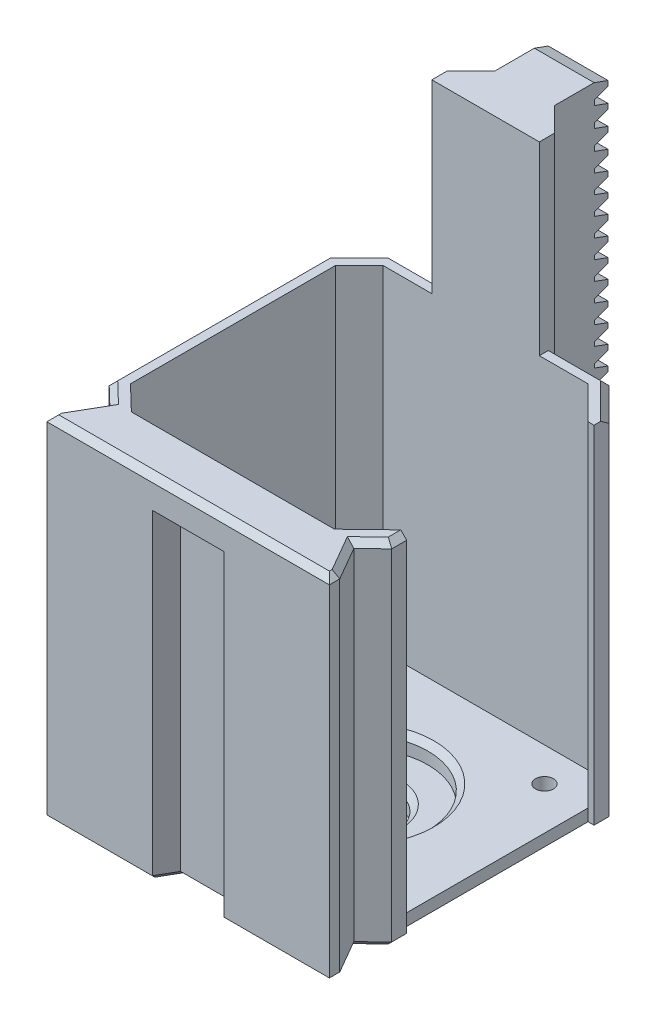
SolidWorks part; units mm, degrees
ref_plane "Front Plane" through (0, 0, 0) normal (0, 0, 1) x (1, 0, 0)
ref_plane "Top Plane" through (0, 0, 0) normal (0, 1, 0) x (1, 0, 0)
ref_plane "Right Plane" through (0, 0, 0) normal (1, 0, 0) x (0, 0, -1)
sketch "Sketch1" plane through (0, 0, 0) normal (0, 1, 0) x (1, 0, 0)
  line L0 (-21.15, 17.15) -> (-17.15, 21.15)
  line L1 (-17, -21.15) -> (17, -21.15)
  line L2 (-21.15, -17.15) -> (-21.15, 17.15)
  line L3 (-17.15, 21.15) -> (17.15, 21.15)
  line L4 (21.15, -17.15) -> (21.15, 17.15)
  line L5 (-21.15, -21.15) -> (21.15, 21.15) construction
  line L6 (-21.15, 21.15) -> (21.15, -21.15) construction
  line L7 (-21.15, -17.15) -> (-17, -21.15)
  line L8 (17, -21.15) -> (21.15, -17.15)
  line L9 (17.15, 21.15) -> (21.15, 17.15)
  circle A0 centre (-15.5, 15.5) radius 1.5
  circle A1 centre (15.5, 15.5) radius 1.5
  circle A2 centre (15.5, -15.5) radius 1.5
  circle A3 centre (-15.5, -15.5) radius 1.5
  circle A4 centre (0, 0) radius 11.5
  point P0 (0, 0)
  dimension "D3" = 3
  dimension "D4" = 3
  dimension "D9" = 3
  dimension "D10" = 3
  dimension "D12" = 23
  dimension "D1" = 42.3
  dimension "D2" = 42.3
  dimension "D11" = 31
  dimension "D13" = 34
  dimension "D6" = 4
  dimension "D7" = 4
extrude "Mount Face Extrude" add sketch "Sketch1" along normal blind 3
chamfer "Bracket Mount Hole Chamfer" distance 0.75 angle 45 4 edges at (-15.5, 0, -14) (15.5, 0, -14) (15.5, 0, 17) (-15.5, 0, 17)
sketch "Sketch5" plane through (0, 0, 0) normal (0, 1, 0) x (1, 0, 0)
  line L0 (21.15, -17.15) -> (22.65, -15.7042)
  line L1 (23.65, -14.7404) -> (23.65, 14.65) construction
  line L3 (-24.65, -28.65) -> (24.65, -28.65) construction
  line L5 (-23.65, -26.9179) -> (-23.65, -28.65)
  line L6 (-23.65, -28.65) -> (23.65, -28.65)
  line L7 (23.65, -28.65) -> (23.65, -26.9179)
  line L8 (-23.65, -26.9179) -> (-24.65, -28.65) construction
  line L9 (24.65, -28.65) -> (23.65, -26.9179) construction
  line L10 (22.65, 15.65) -> (23.65, 15.65)
  line L11 (22.65, -15.7042) -> (23.65, -15.7042)
  line L12 (23.65, 14.65) -> (23.65, 15.65) construction
  line L13 (22.65, 15.65) -> (23.65, 14.65) construction
  line L14 (23.65, -15.7042) -> (23.65, -14.7404) construction
  line L15 (22.65, -15.7042) -> (23.65, -14.7404) construction
  line L16 (-23.65, 18.1855) -> (-23.65, -18.2126)
  line L17 (-23.65, -18.2126) -> (-18.0087, -23.65)
  line L18 (-18.0087, -23.65) -> (18.0087, -23.65)
  line L19 (18.0087, -23.65) -> (23.65, -18.2126)
  line L20 (23.65, -18.2126) -> (23.65, 18.1855)
  line L21 (23.65, 18.1855) -> (18.1855, 23.65)
  line L22 (18.1855, 23.65) -> (-18.1855, 23.65)
  line L23 (-18.1855, 23.65) -> (-23.65, 18.1855)
  line L24 (-23.65, 14.65) -> (-23.65, -18.2126)
  line L25 (-23.65, -18.2126) -> (-20.4209, -21.325)
  line L26 (-18.0087, -23.65) -> (18.0087, -23.65) construction
  line L27 (20.4209, -21.325) -> (23.65, -18.2126)
  line L28 (23.65, -18.2126) -> (23.65, -15.7042)
  line L29 (23.65, 18.1855) -> (18.1855, 23.65)
  line L30 (18.1855, 23.65) -> (-18.1855, 23.65)
  line L31 (-18.1855, 23.65) -> (-23.65, 18.1855)
  line L32 (-21.15, 17.15) -> (-23.65, 14.65) construction
  line L33 (21.15, 17.15) -> (22.65, 15.65)
  line L34 (-23.65, 18.1855) -> (-23.65, 14.65)
  line L35 (23.65, 15.65) -> (23.65, 18.1855)
  line L36 (-23.65, -26.9179) -> (-20.4209, -21.325)
  line L38 (20.4209, -21.325) -> (23.65, -26.9179)
  line L40 (-21.15, 17.15) -> (-21.15, -17.15)
  line L41 (-21.15, -17.15) -> (-17, -21.15)
  line L42 (-17, -21.15) -> (17, -21.15)
  line L43 (17, -21.15) -> (21.15, -17.15)
  line L44 (21.15, -17.15) -> (21.15, 17.15)
  line L45 (21.15, 17.15) -> (17.15, 21.15)
  line L46 (17.15, 21.15) -> (-17.15, 21.15)
  line L47 (-17.15, 21.15) -> (-21.15, 17.15)
  line L48 (-21.15, 17.15) -> (-21.15, -17.15)
  line L49 (-21.15, -17.15) -> (-17, -21.15)
  line L50 (-17, -21.15) -> (17, -21.15)
  line L51 (17, -21.15) -> (21.15, -17.15)
  line L52 (21.15, -17.15) -> (21.15, 17.15) construction
  line L53 (21.15, 17.15) -> (17.15, 21.15)
  line L54 (17.15, 21.15) -> (-17.15, 21.15)
  line L55 (-17.15, 21.15) -> (-21.15, 17.15)
  line L60 (-20.4209, -21.325) -> (-18.0087, -23.65) construction
  line L61 (18.0087, -23.65) -> (20.4209, -21.325) construction
  point P32 (0, -28.65)
  dimension "D3" = 47.3
  dimension "D4" = 60
  dimension "D5" = 47.3
  dimension "D6" = 1
  dimension "D7" = 5
  dimension "D8" = 1
  dimension "D1" = 2.5
  dimension "D2" = 0
extrude "Main Body Extrude" add sketch "Sketch5" along normal blind 59
sketch "Sketch37" plane through (0, 0, 0) normal (0, -1, 0) x (1, 0, 0)
  line L0 (21.15, -17.15) -> (22.65, -15.65) construction
  line L1 (21.15, 17.15) -> (21.15, -17.15) construction
  line L2 (22.65, 15.7042) -> (21.15, 17.15) construction
  line L3 (21.15, -17.15) -> (22.65, -15.65)
  line L4 (21.15, 17.15) -> (21.15, -17.15)
  line L5 (22.65, 15.7042) -> (21.15, 17.15)
  line L6 (22.65, 15.7042) -> (22.65, -15.65)
extrude "Front Face Fill in Extrude" add sketch "Sketch37" against normal up to surface (3 mm away) up to face at (0, 3, 0)
sketch "Sketch39" plane through (0, 0, 0) normal (0, -1, 0) x (1, 0, 0)
  line L0 (-6, 28.65) -> (-4.2679, 25.65)
  line L1 (-23.65, 28.65) -> (23.65, 28.65) construction
  line L2 (-4.2679, 25.65) -> (4.2679, 25.65)
  line L3 (4.2679, 25.65) -> (6, 28.65)
  line L4 (6, 28.65) -> (-6, 28.65)
  line L5 (0, 0) -> (0, 25.65) construction
  dimension "D1" = 3
  dimension "D2" = 12
  dimension "D3" = 60
extrude "Limit Tab" cut sketch "Sketch39" against normal offset from surface (54 mm away) 5 up to face at (2.2864, 59, 4.8477)
sketch "Sketch13" plane through (0, 0, 0) normal (1, 0, 0) x (0, 0, -1)
  line L0 (36.65, 6.9244) -> (36.65, 6.0816)
  line L1 (36.65, 6.0816) -> (34.4, 5.2626)
  line L2 (34.4, 5.2626) -> (34.4, 4.6018)
  line L3 (34.4, 4.6018) -> (36.65, 3.7828)
  line L4 (36.65, 10.066) -> (36.65, 9.2232)
  line L5 (36.65, 9.2232) -> (34.4, 8.4042)
  line L6 (34.4, 8.4042) -> (34.4, 7.7434)
  line L7 (34.4, 7.7434) -> (36.65, 6.9244)
  line L8 (36.65, 13.2076) -> (36.65, 12.3648)
  line L9 (36.65, 12.3648) -> (34.4, 11.5458)
  line L10 (34.4, 11.5458) -> (34.4, 10.885)
  line L11 (34.4, 10.885) -> (36.65, 10.066)
  line L12 (36.65, 16.3492) -> (36.65, 15.5064)
  line L13 (36.65, 15.5064) -> (34.4, 14.6874)
  line L14 (34.4, 14.6874) -> (34.4, 14.0266)
  line L15 (34.4, 14.0266) -> (36.65, 13.2076)
  line L16 (36.65, 19.4908) -> (36.65, 18.648)
  line L17 (36.65, 18.648) -> (34.4, 17.829)
  line L18 (34.4, 17.829) -> (34.4, 17.1681)
  line L19 (34.4, 17.1681) -> (36.65, 16.3492)
  line L20 (36.65, 22.6324) -> (36.65, 21.7895)
  line L21 (36.65, 21.7895) -> (34.4, 20.9706)
  line L22 (34.4, 20.9706) -> (34.4, 20.3097)
  line L23 (34.4, 20.3097) -> (36.65, 19.4908)
  line L24 (36.65, 25.774) -> (36.65, 24.9311)
  line L25 (36.65, 24.9311) -> (34.4, 24.1122)
  line L26 (34.4, 24.1122) -> (34.4, 23.4513)
  line L27 (34.4, 23.4513) -> (36.65, 22.6324)
  line L28 (36.65, 28.9156) -> (36.65, 28.0727)
  line L29 (36.65, 28.0727) -> (34.4, 27.2538)
  line L30 (34.4, 27.2538) -> (34.4, 26.5929)
  line L31 (34.4, 26.5929) -> (36.65, 25.774)
  line L32 (36.65, 32.0572) -> (36.65, 31.2143)
  line L33 (36.65, 31.2143) -> (34.4, 30.3954)
  line L34 (34.4, 30.3954) -> (34.4, 29.7345)
  line L35 (34.4, 29.7345) -> (36.65, 28.9156)
  line L36 (36.65, 35.1988) -> (36.65, 34.3559)
  line L37 (36.65, 34.3559) -> (34.4, 33.537)
  line L38 (34.4, 33.537) -> (34.4, 32.8761)
  line L39 (34.4, 32.8761) -> (36.65, 32.0572)
  line L40 (36.65, 38.3404) -> (36.65, 37.4975)
  line L41 (36.65, 37.4975) -> (34.4, 36.6786)
  line L42 (34.4, 36.6786) -> (34.4, 36.0177)
  line L43 (34.4, 36.0177) -> (36.65, 35.1988)
  line L44 (36.65, 41.482) -> (36.65, 40.6391)
  line L45 (36.65, 40.6391) -> (34.4, 39.8202)
  line L46 (34.4, 39.8202) -> (34.4, 39.1593)
  line L47 (34.4, 39.1593) -> (36.65, 38.3404)
  line L48 (36.65, 44.6235) -> (36.65, 43.7807)
  line L49 (36.65, 43.7807) -> (34.4, 42.9618)
  line L50 (34.4, 42.9618) -> (34.4, 42.3009)
  line L51 (34.4, 42.3009) -> (36.65, 41.482)
  line L52 (36.65, 47.7651) -> (36.65, 46.9223)
  line L53 (36.65, 46.9223) -> (34.4, 46.1034)
  line L54 (34.4, 46.1034) -> (34.4, 45.4425)
  line L55 (34.4, 45.4425) -> (36.65, 44.6235)
  line L56 (36.65, 50.9067) -> (36.65, 50.0639)
  line L57 (36.65, 50.0639) -> (34.4, 49.2449)
  line L58 (34.4, 49.2449) -> (34.4, 48.5841)
  line L59 (34.4, 48.5841) -> (36.65, 47.7651)
  line L60 (36.65, 54.0483) -> (36.65, 53.2055)
  line L61 (36.65, 53.2055) -> (34.4, 52.3865)
  line L62 (34.4, 52.3865) -> (34.4, 51.7257)
  line L63 (34.4, 51.7257) -> (36.65, 50.9067)
  line L64 (36.65, 57.1899) -> (36.65, 56.3471)
  line L65 (36.65, 56.3471) -> (34.4, 55.5281)
  line L66 (34.4, 55.5281) -> (34.4, 54.8673)
  line L67 (34.4, 54.8673) -> (36.65, 54.0483)
  line L68 (36.65, 60.3315) -> (36.65, 59.4887)
  line L69 (36.65, 59.4887) -> (34.4, 58.6697)
  line L70 (34.4, 58.6697) -> (34.4, 58.0089)
  line L71 (34.4, 58.0089) -> (36.65, 57.1899)
  line L72 (36.65, 63.4731) -> (36.65, 62.6302)
  line L73 (36.65, 62.6302) -> (34.4, 61.8113)
  line L74 (34.4, 61.8113) -> (34.4, 61.1504)
  line L75 (34.4, 61.1504) -> (36.65, 60.3315)
  line L76 (36.65, 66.6147) -> (36.65, 65.7718)
  line L77 (36.65, 65.7718) -> (34.4, 64.9529)
  line L78 (34.4, 64.9529) -> (34.4, 64.292)
  line L79 (34.4, 64.292) -> (36.65, 63.4731)
  line L80 (36.65, 69.7563) -> (36.65, 68.9134)
  line L81 (36.65, 68.9134) -> (34.4, 68.0945)
  line L82 (34.4, 68.0945) -> (34.4, 67.4336)
  line L83 (34.4, 67.4336) -> (36.65, 66.6147)
  line L84 (36.65, 72.8979) -> (36.65, 72.055)
  line L85 (36.65, 72.055) -> (34.4, 71.2361)
  line L86 (34.4, 71.2361) -> (34.4, 70.5752)
  line L87 (34.4, 70.5752) -> (36.65, 69.7563)
  line L88 (36.65, 76.0395) -> (36.65, 75.1966)
  line L89 (36.65, 75.1966) -> (34.4, 74.3777)
  line L90 (34.4, 74.3777) -> (34.4, 73.7168)
  line L91 (34.4, 73.7168) -> (36.65, 72.8979)
  line L92 (36.65, 79.1811) -> (36.65, 78.3382)
  line L93 (36.65, 78.3382) -> (34.4, 77.5193)
  line L94 (34.4, 77.5193) -> (34.4, 76.8584)
  line L95 (34.4, 76.8584) -> (36.65, 76.0395)
  line L98 (36.65, 3.7828) -> (36.65, 2.94)
  line L99 (36.65, 2.94) -> (34.4, 2.1211)
  line L100 (34.4, 2.1211) -> (34.4, 1.4602)
  line L101 (34.4, 1.4602) -> (36.65, 0.6413)
  line L102 (36.65, 0.6413) -> (36.65, 0)
  line L103 (36.65, 0) -> (23.65, 0)
  line L104 (23.65, 0) -> (23.65, 90)
  line L105 (23.65, 59) -> (23.65, 0) construction
  line L108 (34.4, 80) -> (36.65, 79.1811)
  line L146 (36.65, 82.5046) -> (36.65, 81.6618)
  line L147 (18.1855, 0) -> (23.65, 0) construction
  line L148 (34.4, 80.6609) -> (34.4, 80) [skipped]
  line L149 (36.65, 81.4798) -> (34.4, 80.6609) [skipped]
  line L150 (36.65, 82.3227) -> (36.65, 81.4798) [skipped]
  line L151 (34.4, 83.1416) -> (36.65, 82.3227) [skipped]
  line L152 (36.65, 84.6214) -> (34.4, 83.8025) [skipped]
  line L153 (34.4, 86.2832) -> (36.65, 85.4643) [skipped]
  line L154 (36.65, 87.763) -> (34.4, 86.9441) [skipped]
  line L155 (34.4, 89.4248) -> (36.65, 88.6058) [skipped]
  line L156 (36.65, 90.9046) -> (34.4, 90.0856) [skipped]
  line L157 (34.4, 92.5664) -> (36.65, 91.7474) [skipped]
  line L158 (34.4, 83.8025) -> (34.4, 83.1416) [skipped]
  line L159 (34.4, 86.9441) -> (34.4, 86.2832) [skipped]
  line L160 (36.65, 85.4643) -> (36.65, 84.6214) [skipped]
  line L161 (36.65, 88.6058) -> (36.65, 87.763) [skipped]
  line L162 (34.4, 90.0856) -> (34.4, 89.4248) [skipped]
  line L163 (36.65, 91.7474) -> (36.65, 90.9046) [skipped]
  line L164 (34.4, 93.2272) -> (34.4, 92.5664) [skipped]
  line L165 (36.65, 94.0462) -> (34.4, 93.2272) [skipped]
  line L166 (36.65, 94.889) -> (36.65, 94.0462) [skipped]
  line L167 (34.4, 95.708) -> (36.65, 94.889) [skipped]
  line L168 (34.4, 96.3688) -> (34.4, 95.708) [skipped]
  line L169 (36.65, 97.1878) -> (34.4, 96.3688) [skipped]
  line L170 (36.65, 98.0306) -> (36.65, 97.1878) [skipped]
  line L171 (34.4, 98.8496) -> (36.65, 98.0306) [skipped]
  line L172 (34.4, 99.5104) -> (34.4, 98.8496) [skipped]
  line L173 (36.65, 100.3294) -> (34.4, 99.5104) [skipped]
  line L174 (36.65, 101.1722) -> (36.65, 100.3294) [skipped]
  line L175 (34.4, 101.9911) -> (36.65, 101.1722) [skipped]
  line L176 (34.4, 102.652) -> (34.4, 101.9911) [skipped]
  line L177 (36.65, 110.597) -> (36.65, 109.7541) [skipped]
  line L178 (36.65, 109.7541) -> (34.4, 108.9352) [skipped]
  line L179 (34.4, 108.9352) -> (34.4, 108.2743) [skipped]
  line L180 (34.4, 108.2743) -> (36.65, 107.4554) [skipped]
  line L181 (36.65, 107.4554) -> (36.65, 106.6125) [skipped]
  line L182 (36.65, 106.6125) -> (34.4, 105.7936) [skipped]
  line L183 (34.4, 105.7936) -> (34.4, 105.1327) [skipped]
  line L184 (34.4, 105.1327) -> (36.65, 104.3138) [skipped]
  line L185 (36.65, 104.3138) -> (36.65, 103.471) [skipped]
  line L186 (36.65, 103.471) -> (34.4, 102.652) [skipped]
  line L187 (36.65, 81.6618) -> (34.4, 80.8429)
  line L188 (34.4, 80.8429) -> (34.4, 80)
  line L189 (36.65, 85.8282) -> (36.65, 84.9854)
  line L190 (36.65, 84.9854) -> (34.4, 84.1664)
  line L191 (34.4, 84.1664) -> (34.4, 83.3236)
  line L192 (34.4, 83.3236) -> (36.65, 82.5046)
  line L193 (36.65, 89.1518) -> (36.65, 88.3089)
  line L194 (36.65, 88.3089) -> (34.4, 87.49)
  line L195 (34.4, 87.49) -> (34.4, 86.6472)
  line L196 (34.4, 86.6472) -> (36.65, 85.8282)
  line L200 (34.4, 89.9707) -> (36.65, 89.1518)
  line L210 (23.65, 90) -> (34.3196, 90)
  line L211 (34.4, 89.9707) -> (34.3196, 90)
  point P14 (23.65, 90)
  point P34 (0, 0)
  point P79 (0, 0)
  point P84 (0, 0)
  dimension "D1" = 90
  dimension "D2" = 0.8429
  dimension "D3" = 0.6609
  dimension "D4" = 2.2987
  dimension "D5" = 13
  dimension "D6" = 0.6413
  dimension "D7" = 20
  dimension "D8" = 3.1416
  dimension "D9" = 35
extrude "Rack Extrude" add sketch "Sketch13" against normal mid plane 10
sketch "Rack Line" plane through (0, 0, 0) normal (1, 0, 0) x (0, 0, -1)
  line L0 (35.65, 0) -> (35.65, 90)
  line L1 (23.65, 0) -> (36.65, 0) construction
  line L3 (23.65, 59) -> (23.65, 0) construction
  point P4 (0, 0)
  point P5 (0, 0)
  dimension "D1" = 12
chamfer "Rack Chamfer" distance 4 angle 45 2 edges at (5, 29.5, -23.65) (-5, 29.5, -23.65)
sketch "Sketch15" plane through (0, 59, 0) normal (0, 1, 0) x (1, 0, 0)
  line L0 (-5, 27.65) -> (-9, 23.65)
  line L1 (17.15, 21.15) -> (-17.15, 21.15) construction
  line L2 (-9, 21.15) -> (9, 21.15)
  line L3 (9, 23.65) -> (5, 27.65)
  line L4 (5, 27.65) -> (-5, 27.65)
  line L5 (9, 23.65) -> (5, 27.65) construction
  line L6 (-5, 27.65) -> (-9, 23.65) construction
  line L9 (-9, 23.65) -> (-9, 21.15)
  line L10 (9, 23.65) -> (9, 21.15)
  line L11 (-11.5, 21.15) -> (-9, 21.15) construction
  line L12 (-9, 23.65) -> (-11.5, 21.15) construction
  line L13 (9, 21.15) -> (11.5, 21.15) construction
  line L14 (11.5, 21.15) -> (9, 23.65) construction
  line L15 (-9, 23.65) -> (-18.1855, 23.65) construction
  line L16 (-5, 27.65) -> (-5, 36.65) construction
extrude "Rack Support Base Extrude" add sketch "Sketch15" along normal up to surface (31 mm away) up to face at (0, 90, -28.9848)
sketch "Sketch27" plane through (0, 0, 0) normal (0, -1, 0) x (-1, 0, 0)
  circle A4 centre (0, 0) radius 13.6
  circle A5 centre (0, 0) radius 11.5 construction
  circle A6 centre (0, 0) radius 11.5
  circle A7 centre (0, 0) radius 6
  circle M47 centre (0, 0) radius 11.5
  dimension "D1" = 12
  dimension "D4" = 27.2
extrude "Face Cosmetic Ring Extrude" add sketch "Sketch27" along normal blind 4 contours A4 M47 | A7 M47 region at (13.2153, 0, 0) region at (11.1747, 0, 0)
chamfer "Face Cosmetic Ring Main Chamfer" distance 4 angle 45 1 edges at (0, 0, -13.6)
chamfer "Face Cosmetic Ring Main Through Hole Chamfer" distance 1 angle 45 3 edges at (0, -4, -6) (0, 0, -6) (0, 3, 11.5)
chamfer "Front/Back Face Chamfer" distance 1 angle 45 36 edges at (13.5928, 59, -23.65) (20.9178, 59, -20.9178) (23.65, 59, 16.9584) (22.0354, 59, 19.7688) (0, 59, 28.65) (-22.0354, 59, 19.7688) (-23.65, 59, 0.0135) (-20.9178, 59, -20.9178) (-13.5928, 59, -23.65) (-7, 0, -25.65) (-13.5928, 0, -23.65) (-20.9178, 0, -20.9178) (7, 0, -25.65) (13.5928, 0, -23.65) (20.9178, 0, -20.9178) (23.65, 0, -16.9178) (23.15, 0, -15.65) (22.65, 0, 0.0271) (23.15, 0, 15.7042) (23.65, 0, 16.9584) (22.0354, 0, 19.7688) (14.825, 0, 28.65) (5.134, 0, 27.15) (0, 0, 25.65) (-5.134, 0, 27.15) (-14.825, 0, 28.65) (-22.0354, 0, 19.7688) (-23.65, 0, 0.0135) (23.65, 59, 27.784) (-23.65, 59, 27.784) (23.65, 0, 27.784) (-23.65, 0, 27.784) (22.0354, 0, 24.1215) (-22.0354, 0, 24.1215) (22.0354, 59, 24.1215) (-22.0354, 59, 24.1215)
